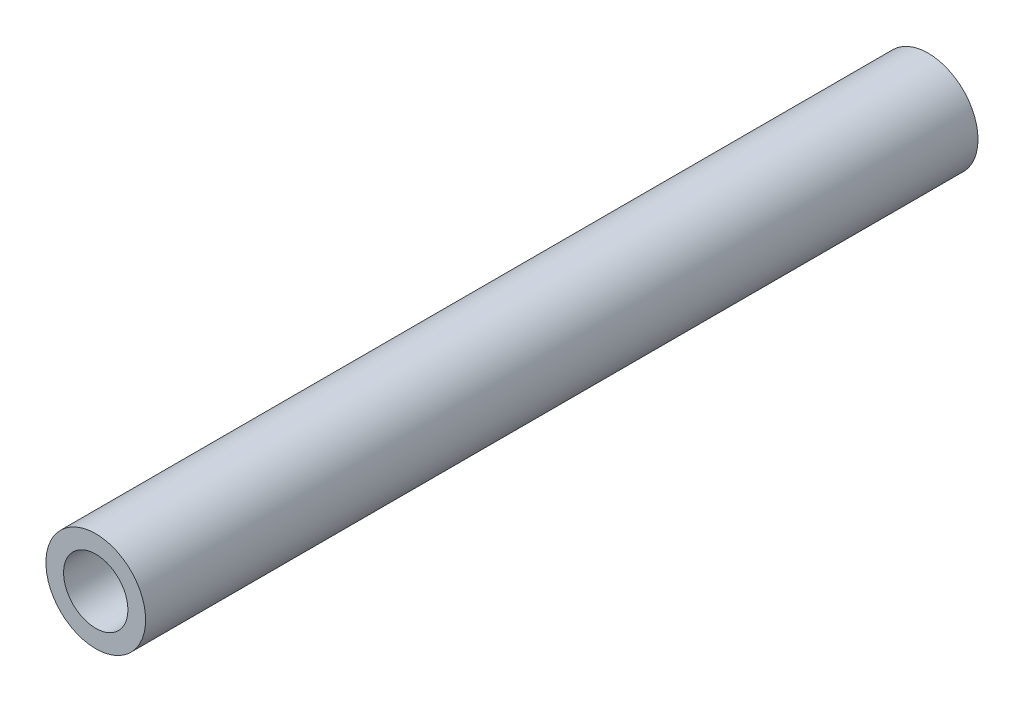
SolidWorks part; units mm, degrees
material "PE High Density"
ref_plane "Front" through (0, 0, 0) normal (0, 0, 1) x (1, 0, 0)
ref_plane "Top" through (0, 0, 0) normal (0, 1, 0) x (1, 0, 0)
ref_plane "Right" through (0, 0, 0) normal (1, 0, 0) x (0, 0, -1)
ref_axis "Axis1" through (0, 0, 55) along (0, 0, -1)
sketch "Sketch1" plane through (0, 0, 0) normal (0, 0, 1) x (1, 0, 0)
  circle A0 centre (0, 0) radius 2.5804
  circle A1 centre (0, 0) radius 4
  dimension "D1" = 8
  dimension "D2" = 5.1608
extrude "Boss-Extrude1" add sketch "Sketch1" along normal blind 66.802
